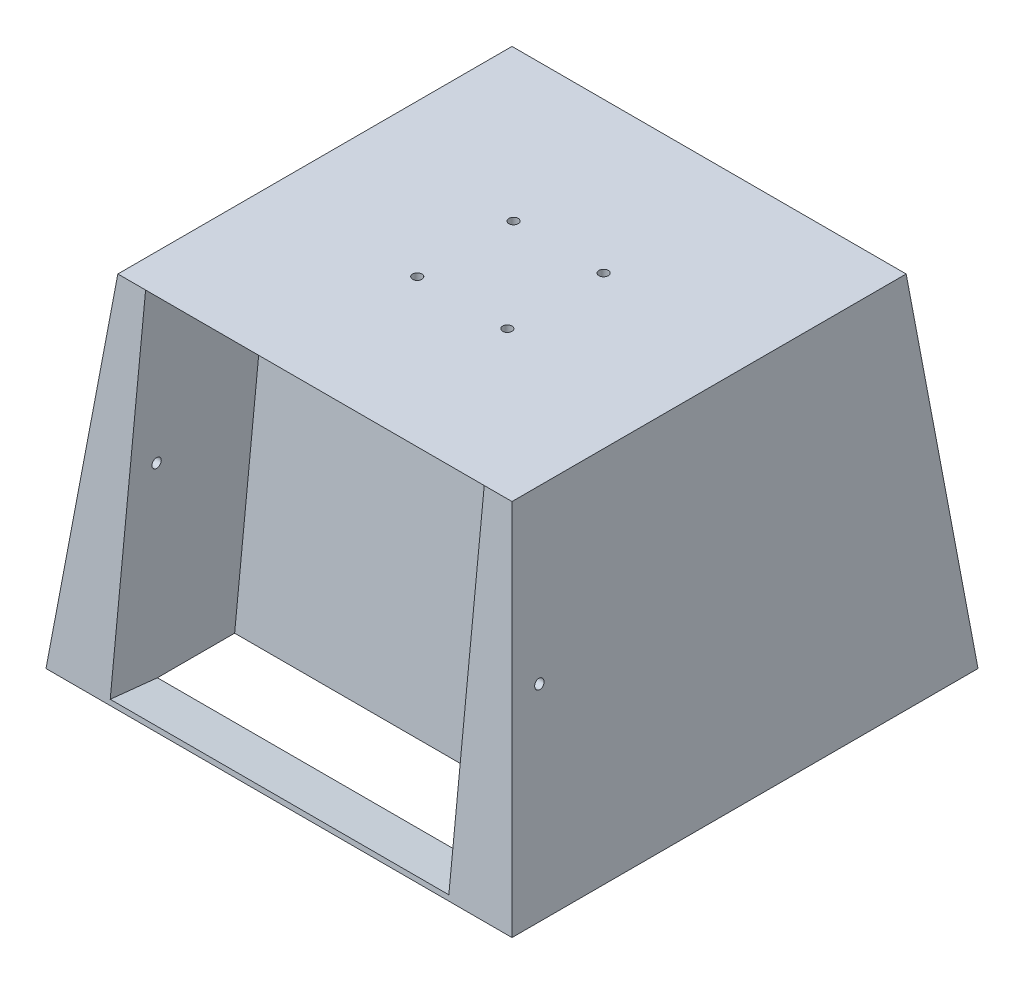
SolidWorks part; units mm, degrees
ref_plane "Front Plane" through (0, 0, 0) normal (0, 0, 1) x (1, 0, 0)
ref_plane "Top Plane" through (0, 0, 0) normal (0, 1, 0) x (1, 0, 0)
ref_plane "Right Plane" through (0, 0, 0) normal (1, 0, 0) x (0, 0, -1)
sketch "Sketch1" plane through (0, 0, 0) normal (0, 1, 0) x (1, 0, 0)
  line L1 (-75, -75) -> (75, -75)
  line L2 (-75, -75) -> (-75, 75)
  line L3 (-75, 75) -> (75, 75)
  line L4 (75, -75) -> (75, 75)
  line L5 (-75, -75) -> (75, 75) construction
  line L6 (-75, 75) -> (75, -75) construction
  point P0 (0, 0)
  dimension "D3" = 150
  dimension "D1" = 150
  dimension "D2" = 150
extrude "Boss-Extrude1" add sketch "Sketch1" along normal blind 110 draft 6 contours L3 L4 L1 L2
sketch "Sketch12" plane through (0, 7.7967, -74.1805) normal (0, 0.1045, -0.9945) x (-1, 0, 0)
  line L0 (-63.4385, 102.7663) -> (63.4385, 102.7663)
  line L1 (63.4385, 102.7663) -> (75, -7.8396)
  line L2 (75, -7.8396) -> (-75, -7.8396)
  line L3 (-75, -7.8396) -> (-63.4385, 102.7663)
  dimension "D1" = 150
  dimension "D2" = 111.2085
  dimension "D3" = 126.8771
sketch "Sketch14" plane through (0, 7.7967, 74.1805) normal (0, 0.1045, 0.9945) x (1, 0, 0)
  line L0 (-63.4385, 102.7663) -> (63.4385, 102.7663) construction
  line L1 (-54.5, -6.2337) -> (54.5, -6.2337)
  line L2 (-54.5, -6.2337) -> (-54.5, 102.7663)
  line L3 (-54.5, 102.7663) -> (54.5, 102.7663)
  line L4 (54.5, -6.2337) -> (54.5, 102.7663)
  line L5 (-54.5, -6.2337) -> (54.5, 102.7663) construction
  line L6 (-54.5, 102.7663) -> (54.5, -6.2337) construction
  point P0 (0, 48.2663)
  point P5 (0, 102.7663)
  point P8 (0, 102.7663)
  dimension "D1" = 109
  dimension "D2" = 109
extrude "Cut-Extrude2" cut sketch "Sketch14" against normal blind 40
sketch "Sketch17" plane through (0, 0, 0) normal (1, 0, 0) x (0, 0, -1)
  circle A0 centre (-59.8969, 60) radius 1.5
  point P0 (-6.2001, 44.5272)
  point P7 (0, 0)
  dimension "D1" = 3
extrude "Cut-Extrude3" cut sketch "Sketch17" against normal through all both and the other way through all
sketch "Sketch18" plane through (0, 110, 0) normal (0, 1, 0) x (1, 0, 0)
  line L0 (63.4385, 0) -> (-63.4385, 0) construction
  line L1 (63.4385, -63.4385) -> (63.4385, 63.4385) construction
  line L2 (-63.4385, -63.4385) -> (-63.4385, 63.4385) construction
  line L3 (63.4385, 63.4385) -> (-63.4385, 63.4385) construction
  line L4 (0, 63.4385) -> (0, -63.4385) construction
  line L5 (54.5, -63.4385) -> (-54.5, -63.4385) construction
  circle A0 centre (14.5, 15) radius 1.5
  circle A1 centre (-14.5, 15) radius 1.5
  circle A2 centre (14.5, -16) radius 1.5
  circle A3 centre (-14.5, -16) radius 1.5
  dimension "D1" = 3
  dimension "D4" = 3
  dimension "D2" = 15
  dimension "D3" = 14.5
  dimension "D5" = 31
extrude "Cut-Extrude4" cut sketch "Sketch18" against normal blind 20 contours A1 | A0 | A3 | A2
sketch "Sketch22" plane through (0, 0, 0) normal (0, -1, 0) x (1, 0, 0)
  line L0 (75, -75) -> (-75, -75)
  line L1 (-75, -75) -> (-75, 75)
  line L2 (-75, 75) -> (75, 75)
  line L3 (75, 75) -> (75, -75)
